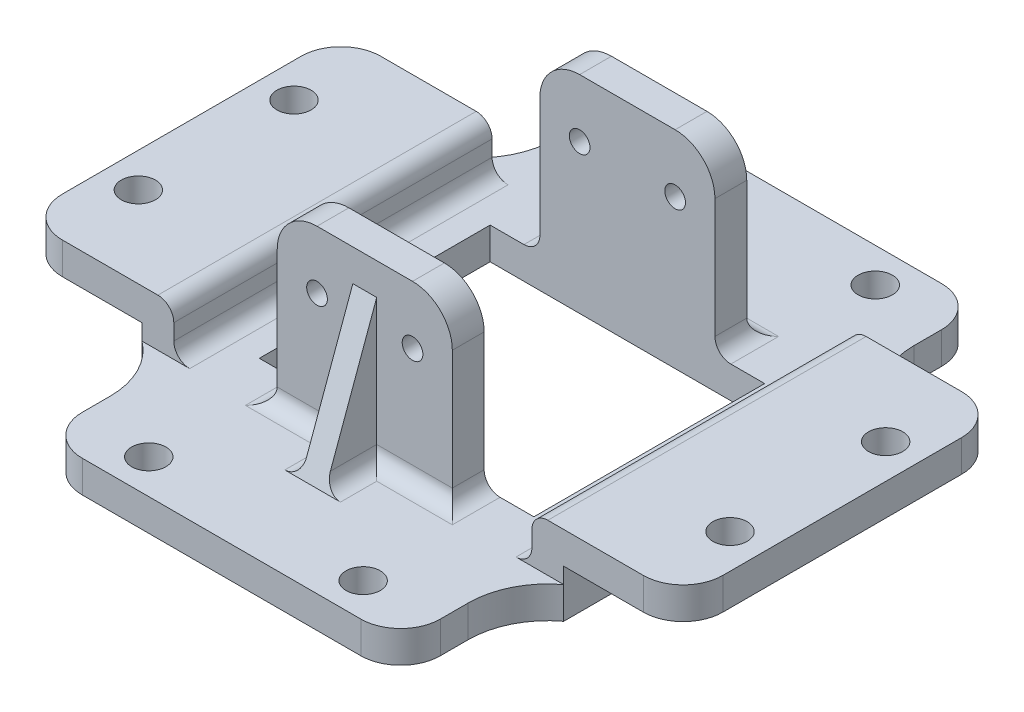
SolidWorks part; units mm, degrees
material "ABS"
ref_plane "Front Plane" through (0, 0, 0) normal (0, 0, 1) x (1, 0, 0)
ref_plane "Top Plane" through (0, 0, 0) normal (0, 1, 0) x (1, 0, 0)
ref_plane "Right Plane" through (0, 0, 0) normal (1, 0, 0) x (0, 0, -1)
sketch "Sketch1" plane through (0, 0, 0) normal (0, 1, 0) x (1, 0, 0)
  line L1 (-17.25, 14.5) -> (17.25, 14.5)
  line L2 (-17.25, 14.5) -> (-17.25, -14.5)
  line L3 (-17.25, -14.5) -> (17.25, -14.5)
  line L4 (17.25, 14.5) -> (17.25, -14.5)
  line L5 (-17.25, 14.5) -> (17.25, -14.5) construction
  line L6 (-17.25, -14.5) -> (17.25, 14.5) construction
  line L7 (22.5, 36.5) -> (-22.5, 36.5)
  line L8 (22.5, 36.5) -> (22.5, -36.5)
  line L9 (22.5, -36.5) -> (-22.5, -36.5)
  line L10 (-22.5, 36.5) -> (-22.5, -36.5)
  line L11 (22.5, 36.5) -> (-22.5, -36.5) construction
  line L12 (22.5, -36.5) -> (-22.5, 36.5) construction
  point P0 (0, 0)
  point P7 (0, 0)
  dimension "D1" = 29
  dimension "D2" = 34.5
  dimension "D3" = 73
  dimension "D4" = 45
extrude "Boss-Extrude1" add sketch "Sketch1" along normal blind 4
sketch "Sketch2" plane through (0, 0, 0) normal (0, 0, 1) x (1, 0, 0)
  line L0 (-22.5, 4) -> (-22.5, 10)
  line L1 (-22.5, 10) -> (-41.5, 10)
  line L2 (-41.5, 10) -> (-41.5, 6)
  line L3 (-41.5, 6) -> (-26.5, 6)
  line L4 (-26.5, 6) -> (-26.5, 0)
  line L5 (-26.5, 0) -> (-22.5, 0)
  line L6 (-22.5, 4) -> (-22.5, 0) construction
  line L7 (-22.5, 0) -> (22.5, 0) construction
  line L8 (-22.5, 0) -> (-22.5, 4)
  dimension "D1" = 4
  dimension "D2" = 19
  dimension "D3" = 6
extrude "Boss-Extrude2" add sketch "Sketch2" along normal mid plane 40
sketch "Sketch6" plane through (0, 4, 0) normal (0, 1, 0) x (1, 0, 0)
  line L0 (-17.25, -14.5) -> (17.25, -14.5) construction
  line L1 (-11, -14.5) -> (11, -14.5)
  line L2 (-11, -14.5) -> (-11, -18.5)
  line L3 (-11, -18.5) -> (11, -18.5)
  line L4 (11, -14.5) -> (11, -18.5)
  line L5 (0, -14.5) -> (0, 0) construction
  dimension "D1" = 22
  dimension "D2" = 4
extrude "Boss-Extrude3" add sketch "Sketch6" along normal blind 22
hole_wizard "#6 Clearance Hole1" positions "Sketch4" profile "Sketch5" hole size "#6" standard "ANSI Inch" end condition through all
sketch "Sketch4" plane through (0, 6, 0) normal (0, -1, 0) x (-1, 0, 0)
  arc A0 (37.175, -11.1316) -> (37.175, -8.4265) centre (37.175, -9.779) ccw construction
  arc A1 (37.175, 11.1316) -> (37.175, 8.4264) centre (37.175, 9.779) ccw construction
  point P0 (37.175, -9.779)
  point P2 (37.175, 9.779)
sketch "Sketch5" plane through (-37.175, 6, 9.779) normal (1, 0, 0) x (0, 0, -1)
  line L0 (0, 0) -> (0, 20)
  line L1 (0, 20) -> (2.1526, 20)
  line L2 (2.1526, 20) -> (2.1526, 0)
  line L5 (2.1526, 0) -> (0, 0)
  line L11 (0, -6.35) -> (0, 107.95) construction
  dimension "Thru Hole Dia." = 4.3053
  dimension "Thru Hole Depth" = 20
hole_wizard "#6 Clearance Hole2" positions "Sketch7" profile "Sketch8" hole size "#6" standard "ANSI Inch" end condition through all
sketch "Sketch7" plane through (0, 4, 0) normal (0, 1, 0) x (1, 0, 0)
  arc A0 (-14.8229, -32.175) -> (-12.1178, -32.175) centre (-13.4704, -32.175) ccw construction
  arc A1 (12.1178, -32.175) -> (14.8229, -32.175) centre (13.4704, -32.175) ccw construction
  point P0 (-13.4704, -32.175)
  point P2 (13.4704, -32.175)
sketch "Sketch8" plane through (-13.4704, 4, 32.175) normal (1, 0, 0) x (0, 0, 1)
  line L0 (0, 0) -> (0, 4)
  line L1 (0, 4) -> (2.1526, 4)
  line L2 (2.1526, 4) -> (2.1526, 0)
  line L5 (2.1526, 0) -> (0, 0)
  line L11 (0, -6.35) -> (0, 107.95) construction
  dimension "Thru Hole Dia." = 4.3053
  dimension "Thru Hole Depth" = 4
hole_wizard "M2 Clearance Hole1" positions "Sketch9" profile "Sketch10" hole size "M2" standard "ANSI Metric" end condition through all
sketch "Sketch9" plane through (0, 0, 18.5) normal (0, 0, 1) x (1, 0, 0)
  arc A0 (-7.05, 18.7) -> (-4.95, 18.7) centre (-6, 18.7) ccw construction
  arc A1 (4.95, 18.7) -> (7.05, 18.7) centre (6, 18.7) ccw construction
  point P0 (6, 18.7)
  point P2 (-6, 18.7)
sketch "Sketch10" plane through (6, 18.7, 18.5) normal (1, 0, 0) x (0, -1, 0)
  line L0 (0, 0) -> (0, 55)
  line L1 (0, 55) -> (1.3, 55)
  line L2 (1.3, 55) -> (1.3, 0)
  line L5 (1.3, 0) -> (0, 0)
  line L11 (0, -6.35) -> (0, 107.95) construction
  dimension "Thru Hole Dia." = 2.6
  dimension "Thru Hole Depth" = 55
sketch "Sketch12" plane through (0, 0, 0) normal (0, 0, 1) x (1, 0, 0)
  line L0 (-26.5, 0) -> (-41.5, 6)
rib "Rib3" sketch "Sketch12" sketch "Sketch12" thickness 3 extrusion direction parallel to sketch draft on no parameters "D1"=3
sketch "Sketch13" plane through (0, 0, 0) normal (1, 0, 0) x (0, 0, -1)
  line L0 (-25.0515, 4) -> (-18.5, 22)
  line L1 (-18.5, 26) -> (-18.5, 4) construction
  line L2 (-36.5, 4) -> (36.5, 4) construction
  line L3 (-18.5, 26) -> (-14.5, 26) construction
  dimension "D1" = 20
  dimension "D2" = 4
rib "Rib4" sketch "Sketch13" sketch "Sketch13" thickness 3 extrusion direction parallel to sketch draft on no parameters "D1"=3
mirror "Mirror1" about plane through (0, 0, 0) normal (0, 0, 1) of "#6 Clearance Hole2", "Boss-Extrude3", "M2 Clearance Hole1", "Rib4"
mirror "Mirror4" about plane through (0, 0, 0) normal (1, 0, 0) of "Rib3", "Boss-Extrude2", "#6 Clearance Hole1"
fillet "Fillet2" radius 2 16 edges at (-22.5, 4, 0) (-22.5, 10, 0) (11, 4, 16.5) (-6.25, 4, 18.5) (6.25, 4, 18.5) (-11, 4, 16.5) (11, 4, -16.5) (-11, 4, -16.5) (-6.25, 4, -18.5) (6.25, 4, -18.5) (22.5, 10, 0) (22.5, 4, 0) (-1.5, 4, -21.7757) (1.5, 4, -21.7757) (1.5, 4, 21.7757) (-1.5, 4, 21.7757)
fillet "Fillet3" radius 5 12 edges at (-41.5, 8, -20) (-41.5, 8, 20) (22.5, 2, -36.5) (-22.5, 2, -36.5) (22.5, 2, 36.5) (-22.5, 2, 36.5) (11, 26, 16.5) (-11, 26, 16.5) (41.5, 8, 20) (41.5, 8, -20) (-11, 26, -16.5) (11, 26, -16.5)
fillet "Fillet4" radius 10 4 edges at (22.5, 2, 20) (22.5, 2, -20) (-22.5, 2, -20) (-22.5, 2, 20)
